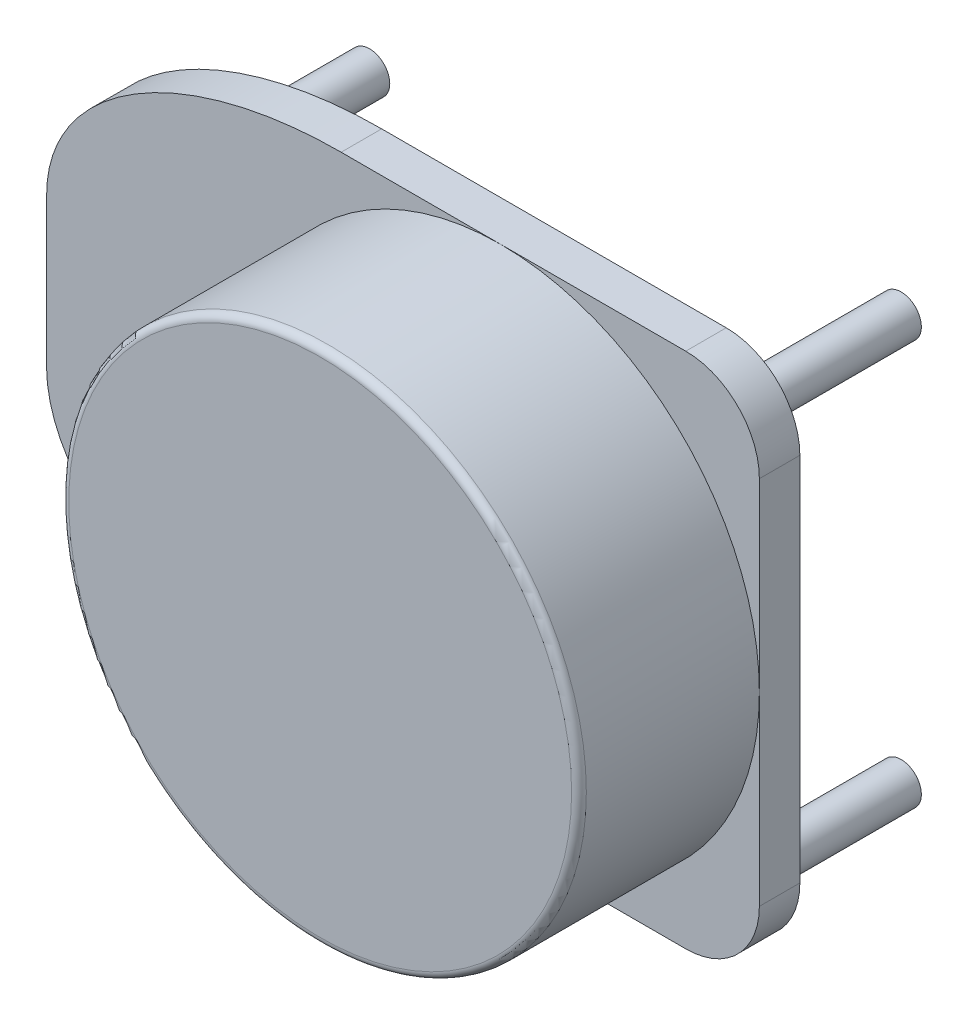
SolidWorks part; units mm, degrees
ref_plane "前视基准面" through (0, 0, 0) normal (0, 0, 1) x (1, 0, 0)
ref_plane "上视基准面" through (0, 0, 0) normal (0, 1, 0) x (1, 0, 0)
ref_plane "右视基准面" through (0, 0, 0) normal (1, 0, 0) x (0, 0, -1)
sketch "草图1" plane through (0, 0, 0) normal (0, 0, 1) x (1, 0, 0)
  line L1 (-10, 0) -> (-96.8, 0)
  line L2 (0, 10) -> (0, 60.3)
  line L3 (-10, 70.3) -> (-96.8, 70.3)
  line L4 (-96.8, 0) -> (-96.8, 70.3)
  line L5 (-35.15, 70.3) -> (-35.15, 0) construction
  circle A1 centre (-35.15, 35.15) radius 35.15
  arc A2 (-10, 0) -> (0, 10) centre (-10, 10) ccw
  arc A3 (0, 60.3) -> (-10, 70.3) centre (-10, 60.3) ccw
  point P11 (0, 0)
  point P14 (0, 70.3)
  dimension "D4" = 70.3
  dimension "D5" = 10
  dimension "D1" = 96.8
  dimension "D2" = 70.3
  dimension "D3" = 35.15
extrude "凸台-拉伸1" add sketch "草图1" against normal blind 5.5 contours L3 L4 L1 A2 L2 A3
extrude "凸台-拉伸2" add sketch "草图1<4>" along normal blind 24.5 contours L5 A1 | A1 L5 region at (-50.0681, 35.15, 0) region at (-20.2319, 35.15, 0)
sketch "草图1<4>" plane through (0, 0, 0) normal (0, 0, 1) x (1, 0, 0) same geometry as "草图1"
fillet "圆角1" radius 25 2 edges at (-96.8, 70.3, -2.75) (-96.8, 0, -2.75) second distance 40 first distance on face at (-96.8, 35.15, -2.75)
fillet "圆角2" radius 1 1 edges at (0, 35.15, 24.5)
sketch "草图2" plane through (0, 0, -5.5) normal (0, 0, -1) x (-1, 0, 0)
  line L0 (96.8, 35.15) -> (0, 35.15) construction
  line L1 (96.8, 25) -> (96.8, 45.3) construction
  line L2 (0, 10) -> (0, 60.3) construction
  circle A0 centre (79.45, 15.15) radius 2.75
  circle A1 centre (7.25, 7.65) radius 2.75
  circle A2 centre (7.25, 62.65) radius 2.75
  circle A3 centre (80.9, 35.15) radius 15.9
  circle A4 centre (79.45, 55.15) radius 2.75
  dimension "D2" = 5.5
  dimension "D3" = 5.5
  dimension "D7" = 31.8
  dimension "D9" = 5.5
  dimension "D10" = 5.5
  dimension "D1" = 55
  dimension "D4" = 27.5
  dimension "D5" = 7.25
  dimension "D6" = 7.25
  dimension "D8" = 40
  dimension "D11" = 20
  dimension "D12" = 72.2
  dimension "D13" = 72.2
extrude "凸台-拉伸3" add sketch "草图2" along normal blind 15.5 contours A3 L0 | L0 A3 region at (-80.9, 28.4018, -5.5) region at (-80.9, 41.8982, -5.5)
extrude "凸台-拉伸4" add sketch "草图2<3>" along normal blind 21 contours A0 | A1 | A2 | A4 region at (-79.45, 15.15, -5.5) region at (-7.25, 7.65, -5.5) region at (-7.25, 62.65, -5.5) region at (-79.45, 55.15, -5.5)
sketch "草图2<3>" plane through (0, 0, -5.5) normal (0, 0, -1) x (-1, 0, 0) same geometry as "草图2"
